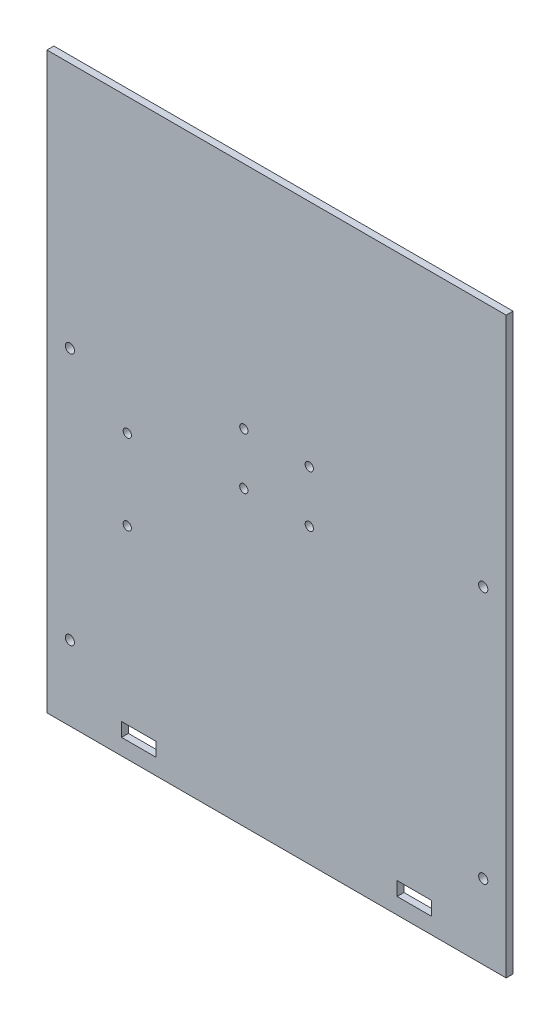
SolidWorks part; units mm, degrees
material "Balsa"
ref_plane "Plano frontal" through (0, 0, 0) normal (0, 0, 1) x (1, 0, 0)
ref_plane "Plano superior" through (0, 0, 0) normal (0, 1, 0) x (1, 0, 0)
ref_plane "Plano direito" through (0, 0, 0) normal (1, 0, 0) x (0, 0, -1)
sketch "Esboço1" plane through (0, 0, 0) normal (0, 0, 1) x (1, 0, 0)
  line L0 (-100, 125) -> (100, 125)
  line L1 (0, 0) -> (0, -105.1003) construction
  line L2 (-100, 125) -> (-100, -125)
  line L3 (67.5, -118) -> (52.5, -112) construction
  line L4 (100, 125) -> (100, -125)
  line L5 (-100, 125) -> (100, -125) construction
  line L6 (-100, -125) -> (100, 125) construction
  line L7 (-67.5, -112) -> (-52.5, -112)
  line L8 (-67.5, -112) -> (-67.5, -118)
  line L9 (-67.5, -118) -> (-52.5, -118)
  line L10 (-52.5, -112) -> (-52.5, -118)
  line L11 (-100, -125) -> (100, -125)
  line L12 (-67.5, -112) -> (-52.5, -118) construction
  line L13 (-14.25, 25) -> (14.25, 25) construction
  line L14 (-67.5, -118) -> (-52.5, -112) construction
  line L15 (67.5, -112) -> (52.5, -118) construction
  line L16 (52.5, -112) -> (52.5, -118)
  line L17 (67.5, -118) -> (52.5, -118)
  line L18 (67.5, -112) -> (67.5, -118)
  line L19 (67.5, -112) -> (52.5, -112)
  line L20 (-52.5, -118) -> (52.5, -118) construction
  circle A0 centre (-14.25, 25) radius 1.8
  circle A1 centre (14.25, 25) radius 1.8
  circle A2 centre (14.25, 2.5) radius 1.8
  circle A3 centre (-14.25, 2.5) radius 1.8
  circle A4 centre (-65, -2) radius 1.8
  circle A5 centre (-65, -37) radius 1.8
  circle A6 centre (-90, -92.5) radius 2
  circle A7 centre (-90, 17.5) radius 2
  circle A8 centre (90, 17.5) radius 2
  circle A9 centre (90, -92.5) radius 2
  point P0 (0, 0)
  point P6 (0, -16.4394)
  point P7 (0, 125)
  point P15 (0, 25)
  point P33 (-60, -115)
  point P40 (60, -115)
  point P41 (0, -118)
  dimension "D6" = 3.6
  dimension "D9" = 35
  dimension "D11" = 3.6
  dimension "D16" = 4
  dimension "D1" = 200
  dimension "D2" = 250
  dimension "D5" = 100
  dimension "D7" = 28.5
  dimension "D8" = 22.5
  dimension "D10" = 123
  dimension "D12" = 35
  dimension "D13" = 110
  dimension "D14" = 32.5
  dimension "D15" = 10
  dimension "D17" = 6
  dimension "D18" = 15
  dimension "D19" = 40
  dimension "D20" = 10
  dimension "D3" = 2
  dimension "D4" = 2
extrude "Ressalto-extrusão1" add sketch "Esboço1" along normal blind 3
